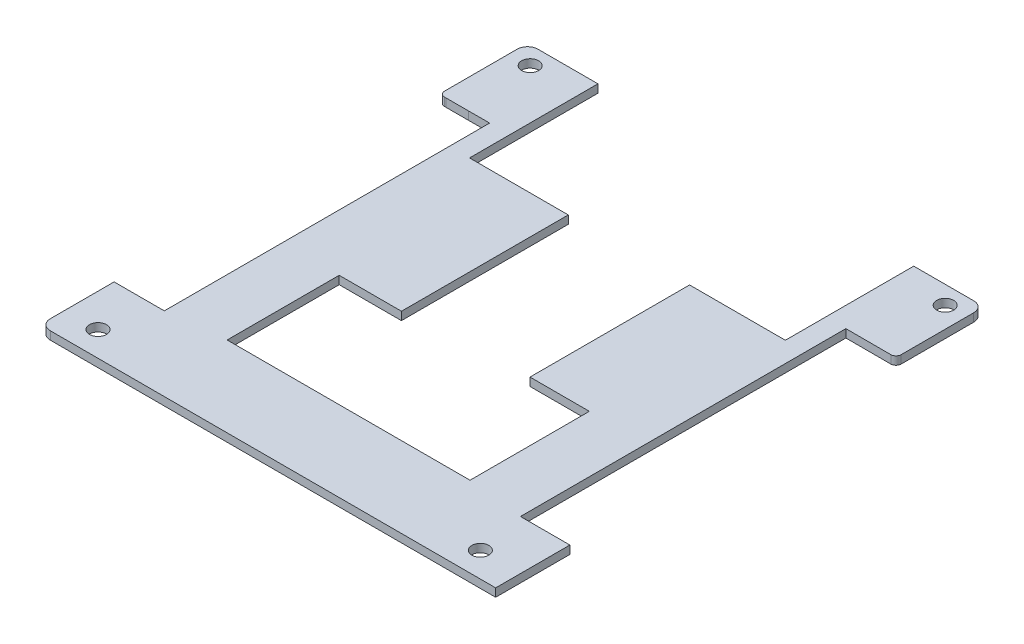
SolidWorks part; units mm, degrees
material "Copper"
ref_plane "Front Plane" through (0, 0, 0) normal (0, 0, 1) x (1, 0, 0)
ref_plane "Top Plane" through (0, 0, 0) normal (0, 1, 0) x (1, 0, 0)
ref_plane "Right Plane" through (0, 0, 0) normal (1, 0, 0) x (0, 0, -1)
sketch "Sketch1" plane through (0, 0, 0) normal (0, 1, 0) x (1, 0, 0)
  line L0 (-38.395, 30) -> (-42.73, 30)
  line L1 (-44, 31.27) -> (-44, 45)
  line L2 (42, 47) -> (30.435, 47)
  line L3 (44, 45) -> (44, 32)
  line L4 (44, 32) -> (44, 31.0156)
  line L5 (42.9984, 30.0156) -> (33.8256, 30.0304)
  line L6 (32.824, 29.0304) -> (32.824, -30.454)
  line L7 (-44, -38.977) -> (-44, -32.454)
  line L8 (-42, -47) -> (43.8497, -47)
  line L9 (-44, -45) -> (-44, -38.977)
  line L10 (-43, -31.454) -> (-36.1, -31.454)
  line L11 (43.8497, -37) -> (43.8497, -32.454)
  line L12 (42.8497, -31.454) -> (36.1, -31.454)
  line L13 (23.409, -31.5) -> (-23.409, -31.5)
  line L14 (-11.409, -9.9) -> (-23.409, -9.9)
  line L15 (30.435, 22.2554) -> (11.9708, 22.2554)
  line L16 (-11.409, -9.9) -> (-11.409, 22.2554)
  line L17 (30.435, 47) -> (30.435, 22.2554)
  line L18 (11.9708, 22.2554) -> (11.9708, -8.5)
  line L19 (-23.409, -31.5) -> (-23.409, -9.9)
  line L20 (11.9708, -8.5) -> (23.409, -8.5)
  line L21 (-36.1, -31.454) -> (-33.824, -31.454)
  line L22 (-32.824, -30.454) -> (-32.824, 29.0115)
  line L23 (-33.8265, 30.0115) -> (-38.395, 30)
  line L24 (-42.73, 30) -> (-43.011, 30.0031)
  line L25 (-44, 31.003) -> (-44, 31.27)
  line L28 (43.8497, -47) -> (43.8497, -37)
  line L33 (33.824, -31.454) -> (36.1, -31.454)
  line L34 (-23.409, 13.2954) -> (-23.409, -31.5) construction
  line L35 (23.409, -31.5) -> (23.409, -8.5)
  line L41 (-42, 47) -> (-30.435, 47)
  line L42 (-30.435, 47) -> (-30.435, 22.2554)
  line L43 (-30.435, 22.2554) -> (-11.409, 22.2554)
  circle A0 centre (40, 43.5) radius 1.6383
  circle A1 centre (-40, 43.5) radius 1.6383
  circle A2 centre (-37.6, -42.2) radius 1.6383
  circle A3 centre (36.1, -42.2) radius 1.6383
  arc A5 (-42, 47) -> (-44, 45) centre (-42, 45) ccw
  arc A6 (44, 45) -> (42, 47) centre (42, 45) ccw
  arc A9 (-43.011, 30.0031) -> (-44, 31.003) centre (-43, 31.003) cw
  arc A10 (-32.824, 29.0115) -> (-33.8265, 30.0115) centre (-33.824, 29.0115) ccw
  arc A11 (-44, -45) -> (-42, -47) centre (-42, -45) ccw
  arc A12 (44, 31.0156) -> (42.9984, 30.0156) centre (43, 31.0156) cw
  arc A14 (33.8256, 30.0304) -> (32.824, 29.0304) centre (33.824, 29.0304) ccw
  arc A15 (43.8497, -32.454) -> (42.8497, -31.454) centre (42.8497, -32.454) ccw
  arc A16 (32.824, -30.454) -> (33.824, -31.454) centre (33.824, -30.454) ccw
  arc A17 (-33.824, -31.454) -> (-32.824, -30.454) centre (-33.824, -30.454) ccw
  arc A18 (-44, -32.454) -> (-43, -31.454) centre (-43, -32.454) cw
  point P37 (-44, 30.014)
  point P48 (-32.824, 30.014)
  point P61 (44, 30.014)
  point P80 (32.824, 30.032)
  point P95 (32.824, -31.454)
  point P98 (-32.824, -31.454)
  dimension "D1" = 1
  dimension "D2" = 73.7
  dimension "D3" = 85.7
  dimension "D4" = 80
  dimension "D5" = 85.7
  dimension "D6" = 19.026
  dimension "D7" = 12
  dimension "D8" = 18.4641
  dimension "D9" = 11.4381
  dimension "D10" = 32.1554
  dimension "D11" = 21.6
extrude "Boss-Extrude1" [suppressed] add sketch "Sketch1" along normal blind 1.575
extrude "Boss-Extrude2" add sketch "Sketch1<2>" along normal blind 1.575
sketch "Sketch1<2>" plane through (0, 0, 0) normal (0, 1, 0) x (1, 0, 0) same geometry as "Sketch1"
sketch "Sketch2" plane through (0, 1.575, 0) normal (0, 1, 0) x (1, 0, 0)
  line L1 (32.8227, -32.694) -> (46.9034, -32.694)
  line L2 (32.8227, -32.694) -> (32.8227, -25.5777)
  line L3 (32.8227, -25.5777) -> (46.9034, -25.5777)
  line L4 (46.9034, -32.694) -> (46.9034, -25.5777)
  line L5 (-47.8402, -23.2727) -> (-32.833, -23.2727)
  line L6 (-47.8402, -23.2727) -> (-47.8402, -32.694)
  line L7 (-47.8402, -32.694) -> (-32.833, -32.694)
  line L8 (-32.833, -23.2727) -> (-32.833, -32.694)
  dimension "D1" = 14.306
  dimension "D2" = 11.027
  dimension "D3" = 11.167
  dimension "D4" = 14.306
extrude "Cut-Extrude1" cut sketch "Sketch2" against normal through all
sketch "Additional PCB material" plane through (0, 1.575, 0) normal (0, 1, 0) x (1, 0, 0)
  line L0 (32.824, 29.0304) -> (32.824, -30.454) construction
  line L1 (31.6745, 31.4781) -> (34.324, 31.4781)
  line L2 (31.6745, 31.4781) -> (31.6745, -33.7352)
  line L3 (31.6745, -33.7352) -> (34.324, -33.7352)
  line L4 (34.324, 31.4781) -> (34.324, -33.7352)
  line L5 (-34.324, 31.564) -> (-32.824, 31.564)
  line L6 (-34.324, 31.564) -> (-34.324, -33.7352)
  line L7 (-34.324, -33.7352) -> (-32.824, -33.7352)
  line L8 (-32.824, 31.564) -> (-32.824, -33.7352)
  dimension "D1" = 1.5
  dimension "D2" = 1.5
  dimension "D3" = 1.5
extrude "Boss-Extrude3" add sketch "Additional PCB material" against normal blind 1.575
